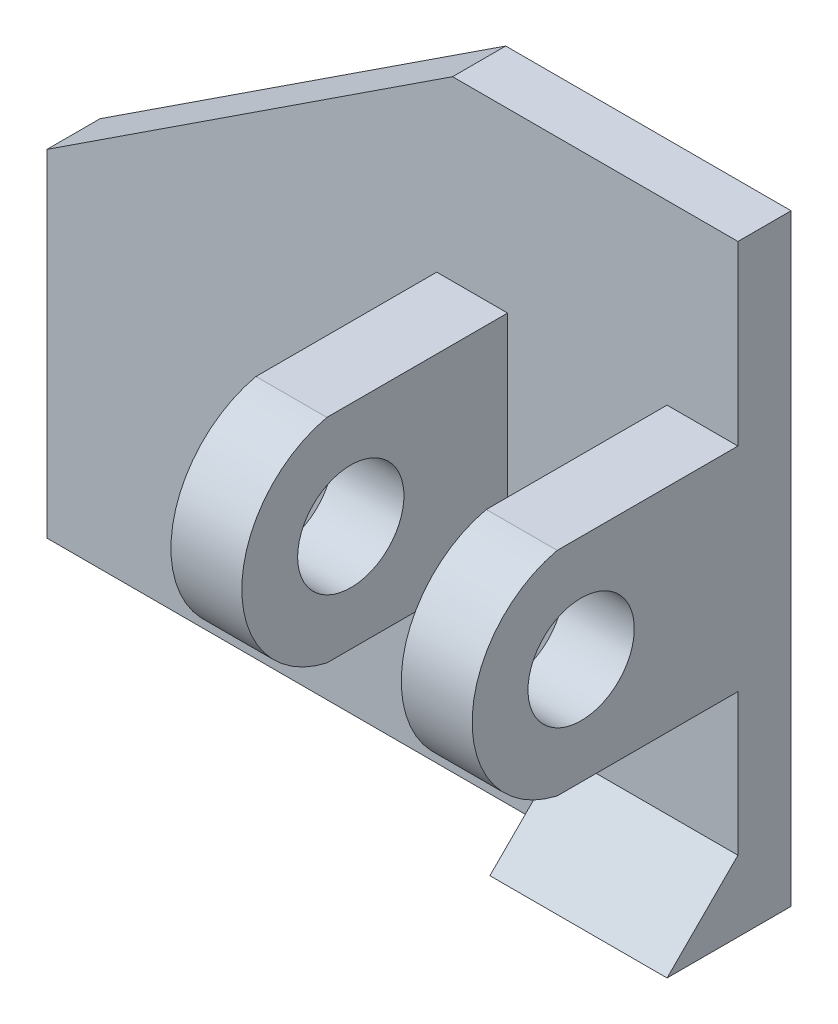
SolidWorks part; units mm, degrees
ref_plane "Plano frontal" through (0, 0, 0) normal (0, 0, 1) x (1, 0, 0)
ref_plane "Plano superior" through (0, 0, 0) normal (0, 1, 0) x (1, 0, 0)
ref_plane "Plano direito" through (0, 0, 0) normal (1, 0, 0) x (0, 0, -1)
sketch "Esboço1" plane through (0, 0, 0) normal (0, 0, 1) x (1, 0, 0)
  line L1 (-24.5, -19) -> (14.5, -19)
  line L2 (-24.5, -19) -> (-24.5, 0)
  line L3 (14.5, -19) -> (4.5, -19)
  line L4 (1.5, 5) -> (-2.5, 5)
  line L5 (-2.5, -7) -> (1.5, -7)
  line L6 (-2.5, -7) -> (-2.5, 5)
  line L7 (-24.5, -19) -> (-15.5, -19)
  line L8 (-24.5, -19) -> (-24.5, -15)
  line L9 (-17, -15) -> (-15.5, -15)
  line L10 (-15.5, -16.5) -> (-15.5, -15)
  line L11 (-1.6053, 15) -> (-24.5, 0)
  line L12 (14.5, 15) -> (14.5, -19)
  line L13 (14.5, -19) -> (4.5, -19)
  line L14 (1.5, 5) -> (1.5, 15)
  line L15 (14.5, -2) -> (14.5, 5)
  line L16 (14.5, 5) -> (10.5, 5)
  line L17 (-2.5, 0) -> (-2.5, 5)
  line L18 (-1.6053, 15) -> (14.5, 15)
  line L19 (14.5, -2) -> (14.5, -7)
  line L20 (14.5, -7) -> (10.5, -7)
  line L21 (-2.5, 0) -> (-2.5, -7)
  line L22 (-2.5, 5) -> (1.5, 5)
  line L23 (1.5, -7) -> (1.5, 5)
  line L24 (14.5, 5) -> (10.5, 5)
  line L25 (14.5, 5) -> (14.5, -7)
  line L26 (14.5, -7) -> (10.5, -7)
  line L27 (10.5, 5) -> (10.5, -7)
  line L28 (1.5, -7) -> (-2.5, -7)
  line L29 (14.5, -19) -> (14.5, -15)
  line L30 (14.5, -15) -> (4.5, -15)
  line L31 (4.5, -19) -> (4.5, -15)
  circle A0 centre (-15.5, -15) radius 1.5
  point P0 (0, 0)
  dimension "D5" = 3
  dimension "D1" = 5
  dimension "D2" = 7
  dimension "D3" = 9
  dimension "D4" = 4
  dimension "D6" = 17
  dimension "D7" = 4
  dimension "D8" = 4
  dimension "D9" = 10
  dimension "D10" = 4
extrude "Ressalto-extrusão1" add sketch "Esboço1" along normal blind 3 contours L27 L16 L12 L11 L2 L1 L20 A0 L23 L5 L6 L4 | L31 L1 L12 L30 region at (-4.5291, -3.4484, 0) region at (9.5, -17, 0)
extrude "Ressalto-extrusão2" add sketch "Esboço1<8>" along normal blind 18 contours L16 L27 L20 L12 | L5 L23 L4 L6 region at (-0.5, -1, 0) region at (12.5, -1, 0)
sketch "Esboço1<8>" plane through (0, 0, 0) normal (0, 0, 1) x (1, 0, 0) same geometry as "Esboço1"
sketch "Esboço2" plane through (14.5, 0, 0) normal (1, 0, 0) x (0, 0, -1)
  line L0 (-18, 5) -> (-3, 5) construction
  line L1 (-18, -7) -> (-3, -7) construction
  line L2 (-10.5, 5) -> (-18, 5)
  line L3 (-18, 5) -> (-18, -7)
  line L4 (-18, -7) -> (-10.5, -7)
  arc A0 (-13.2, 5) -> (-13.2, -7) centre (-11.85, -1) ccw
  circle A1 centre (-11.85, -1) radius 3
  line M5 (-18, 5) -> (-18, -7)
  line M6 (-18, -7) -> (-3, -7)
  dimension "D1" = 6
extrude "Corte-extrusão1" cut sketch "Esboço2" against normal through all and the other way through all contours A0 L2 M5 | A0 L3 M6 | A1 region at (14.5, 3.6365, 16.7616) region at (14.5, -5.6365, 16.7616) region at (14.5, -1, 11.85)
extrude "Ressalto-extrusão3" add sketch "Esboço1<9>" along normal blind 8 contours L31 L1 L12 L30 region at (9.5, -17, 0)
sketch "Esboço1<9>" plane through (0, 0, 0) normal (0, 0, 1) x (1, 0, 0) same geometry as "Esboço1"
chamfer "Chanfro1" distance 5 angle 45 1 edges at (9.5, -15, 8)
